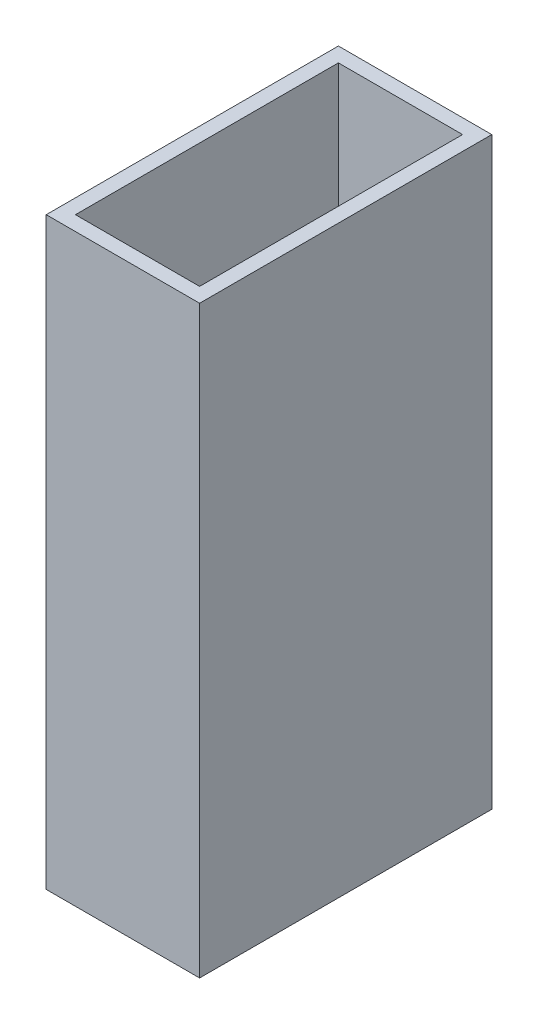
SolidWorks part; units mm, degrees
ref_plane "Front Plane" through (0, 0, 0) normal (0, 0, 1) x (1, 0, 0)
ref_plane "Top Plane" through (0, 0, 0) normal (0, 1, 0) x (1, 0, 0)
ref_plane "Right Plane" through (0, 0, 0) normal (1, 0, 0) x (0, 0, -1)
sketch "Sketch1" plane through (0, 0, 0) normal (0, 1, 0) x (1, 0, 0)
  line L0 (0, 69.5918) -> (0, -86.5306) construction
  line L1 (-26.25, 50) -> (26.25, 50)
  line L2 (-26.25, 50) -> (-26.25, -50)
  line L3 (-26.25, -50) -> (26.25, -50)
  line L4 (26.25, 50) -> (26.25, -50)
  line L5 (-104.4898, 0) -> (80.2041, 0) construction
  point P9 (-104.4898, 0)
  dimension "D1" = 100
  dimension "D2" = 52.5
extrude "Boss-Extrude1" add sketch "Sketch1" along normal blind 200
shell "Shell2" thickness 5 removed face at (0, 200, 0)
